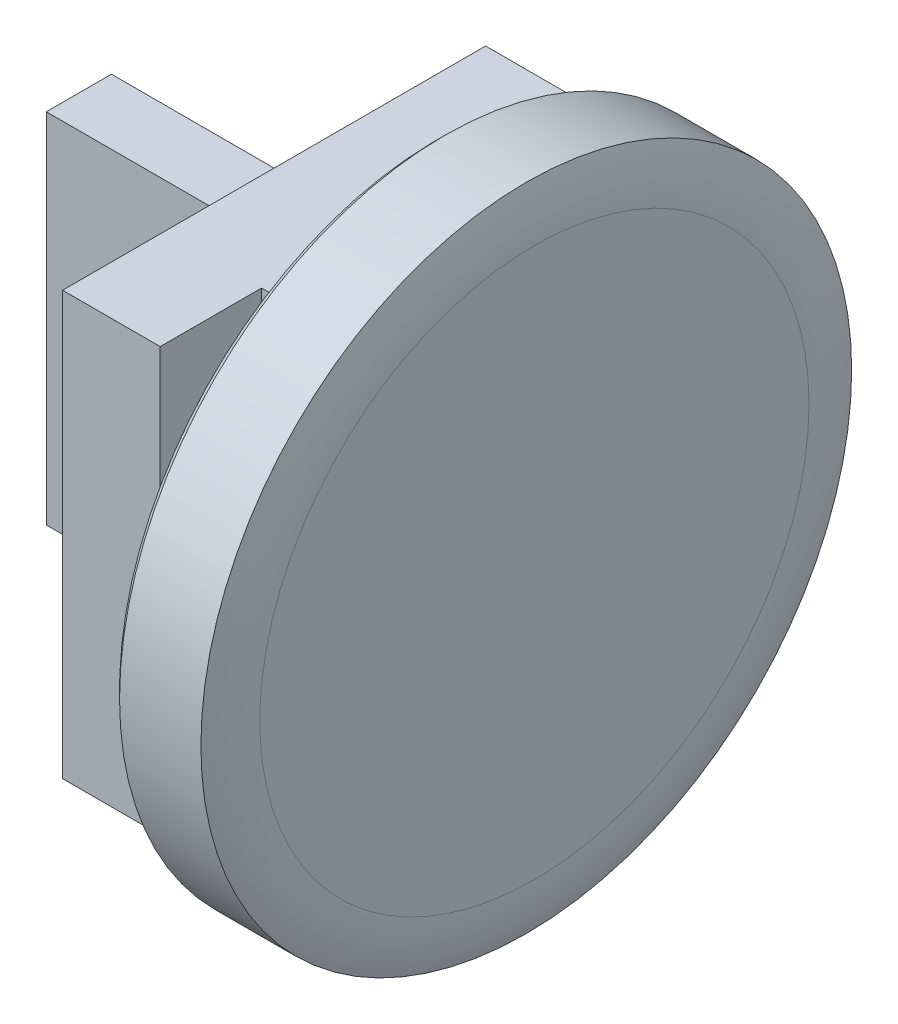
SolidWorks part; units mm, degrees
material "PP Kopolimer"
ref_plane "Front Plane" through (0, 0, 0) normal (0, 0, 1) x (1, 0, 0)
ref_plane "Top Plane" through (0, 0, 0) normal (0, 1, 0) x (1, 0, 0)
ref_plane "Right Plane" through (0, 0, 0) normal (1, 0, 0) x (0, 0, -1)
sketch "Szkic1" plane through (0, 0, 0) normal (0, 1, 0) x (1, 0, 0)
  line L1 (-1.5, -6.5) -> (1.5, -6.5)
  line L2 (-1.5, -6.5) -> (-1.5, 6.5)
  line L3 (-1.5, 6.5) -> (1.5, 6.5)
  line L4 (1.5, -6.5) -> (1.5, 6.5)
  line L5 (-1.5, -6.5) -> (1.5, 6.5) construction
  line L6 (-1.5, 6.5) -> (1.5, -6.5) construction
  point P0 (0, 0)
extrude "Dodanie-wyciągnięcie2" add sketch "Szkic1" along normal blind 13 contours L2 L3 L4 L1
sketch "Szkic3" plane through (1.5, 0, 0) normal (1, 0, 0) x (0, 0, -1)
  line L0 (0, 13) -> (0, 0) construction
  line L1 (-6.5, 13) -> (6.5, 13) construction
  line L3 (-3.3849, 0) -> (3.3849, 0)
  line L4 (-3.3849, 0) -> (-3.3849, 13)
  line L5 (-3.3849, 13) -> (3.3849, 13)
  line L6 (3.3849, 0) -> (3.3849, 13)
  line L7 (-3.3849, 0) -> (3.3849, 13) construction
  line L8 (-3.3849, 13) -> (3.3849, 0) construction
  point P5 (0, 6.5)
extrude "Dodanie-wyciągnięcie3" add sketch "Szkic3" along normal blind 2
sketch "Szkic4" plane through (3.5, 0, 0) normal (1, 0, 0) x (0, 0, -1)
  line L0 (0, 13) -> (0, 0) construction
  line L1 (3.3849, 13) -> (-3.3849, 13) construction
  line L2 (-3.3849, 0) -> (3.3849, 0) construction
  circle A0 centre (0, 6.5) radius 10
extrude "Dodanie-wyciągnięcie4" add sketch "Szkic4" along normal blind 3
chamfer "Sfazowanie1" distance 0.25 angle 45 1 edges at (6.5, 6.5, -10)
chamfer "Sfazowanie2" distance 0.25 angle 45 1 edges at (3.5, 6.5, -10)
fillet "Zaokrąglenie2" radius 5 1 edges at (6.5, 6.5, -9.75)
sketch "Szkic5" plane through (-1.5, 0, 0) normal (-1, 0, 0) x (0, 0, 1)
  line L0 (6.5, 6.5) -> (-6.5, 6.5) construction
  line L1 (6.5, 13) -> (6.5, 0) construction
  line L2 (-6.5, 13) -> (-6.5, 0) construction
  line L4 (-1, 12) -> (1, 12)
  line L5 (-1, 12) -> (-1, 1)
  line L6 (-1, 1) -> (1, 1)
  line L7 (1, 12) -> (1, 1)
  line L8 (-1, 12) -> (1, 1) construction
  line L9 (-1, 1) -> (1, 12) construction
  point P6 (0, 6.5)
  dimension "D1" = 2
  dimension "D2" = 11
extrude "Dodanie-wyciągnięcie5" add sketch "Szkic5" along normal blind 6 contours L7 L6 L5 L4
sketch "Szkic8" plane through (0, 0, -1) normal (0, 0, -1) x (-1, 0, 0)
  line L0 (7.5, 6.5) -> (5, 6.5) construction
  line L1 (7.5, 12) -> (7.5, 1) construction
  line L3 (4.5, 8.5) -> (5.5, 8.5)
  line L4 (4.5, 8.5) -> (4.5, 4.5)
  line L5 (4.5, 4.5) -> (5.5, 4.5)
  line L6 (5.5, 8.5) -> (5.5, 4.5)
  line L7 (4.5, 8.5) -> (5.5, 4.5) construction
  line L8 (4.5, 4.5) -> (5.5, 8.5) construction
extrude "Wytnij-wyciągnięcie1" cut sketch "Szkic8" against normal blind 6
